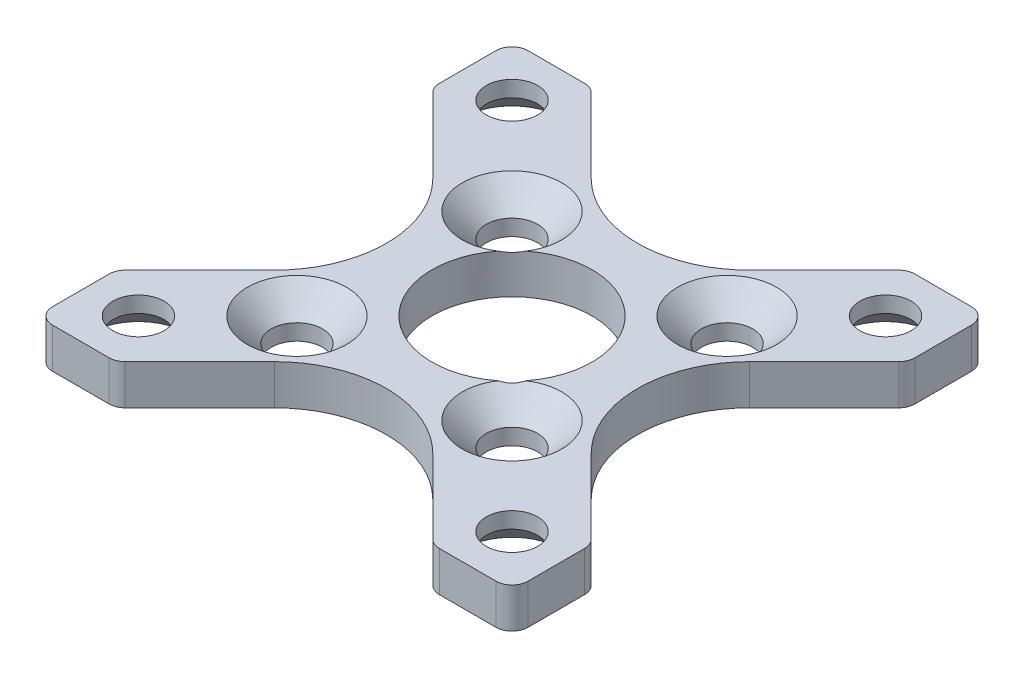
SolidWorks part; units mm, degrees
ref_plane "Front Plane" through (0, 0, 0) normal (0, 0, 1) x (1, 0, 0)
ref_plane "Top Plane" through (0, 0, 0) normal (0, 1, 0) x (1, 0, 0)
ref_plane "Right Plane" through (0, 0, 0) normal (1, 0, 0) x (0, 0, -1)
sketch "Sketch1" plane through (0, 0, 0) normal (0, 1, 0) x (1, 0, 0)
  line L0 (-6.7175, -14.8492) -> (-6.7175, 14.8492) construction
  line L1 (-14.8492, -14.8492) -> (14.8492, -14.8492)
  line L2 (-14.8492, -14.8492) -> (-14.8492, 14.8492)
  line L3 (-14.8492, 14.8492) -> (14.8492, 14.8492)
  line L4 (14.8492, -14.8492) -> (14.8492, 14.8492)
  line L5 (-14.8492, -14.8492) -> (14.8492, 14.8492) construction
  line L6 (-14.8492, 14.8492) -> (14.8492, -14.8492) construction
  line L7 (-14.8492, -6.7175) -> (14.8492, -6.7175) construction
  line L8 (6.7175, 14.8492) -> (6.7175, -14.8492) construction
  line L9 (14.8492, 6.7175) -> (-14.8492, 6.7175) construction
  circle A0 centre (0, 0) radius 5
  circle A1 centre (-5.6569, 5.6569) radius 1.6
  circle A2 centre (5.6569, -5.6569) radius 1.6
  circle A3 centre (-6.7175, -6.7175) radius 1.6
  circle A4 centre (6.7175, 6.7175) radius 1.6
  circle A5 centre (-11.6673, -11.6673) radius 1.6
  circle A6 centre (-11.6673, 11.6673) radius 1.6
  circle A7 centre (11.6673, 11.6673) radius 1.6
  circle A8 centre (11.6673, -11.6673) radius 1.6
  point P0 (0, 0)
  dimension "D3" = 10
  dimension "D7" = 3.2
  dimension "D1" = 42
  dimension "D2" = 13
  dimension "D4" = 13
  dimension "D5" = 11.5
  dimension "D6" = 11.5
  dimension "D8" = 4.5
  dimension "D9" = 4.5
  dimension "D10" = 4.5
  dimension "D11" = 4.5
extrude "Boss-Extrude1" add sketch "Sketch1" along normal blind 2.5
sketch "Sketch2" plane through (0, 2.5, 0) normal (0, 1, 0) x (1, 0, 0)
  line L0 (0, 14.8492) -> (0, -14.8492) construction
  line L1 (14.8492, 14.8492) -> (-14.8492, 14.8492) construction
  line L2 (-14.8492, -14.8492) -> (14.8492, -14.8492) construction
  line L3 (-14.8492, 0) -> (14.8492, 0) construction
  line L5 (-14.8492, 14.8492) -> (-14.8492, -14.8492) construction
  line L6 (14.8492, -14.8492) -> (14.8492, 14.8492) construction
  line L7 (-6.7175, -6.7175) -> (-6.7175, 6.7175) construction
  line L8 (-6.7175, 6.7175) -> (6.7175, 6.7175) construction
  line L9 (6.7175, 6.7175) -> (6.7175, -6.7175) construction
  line L10 (6.7175, -6.7175) -> (-6.7175, -6.7175) construction
  line L11 (-14.8492, -14.8492) -> (14.8492, 14.8492) construction
  line L12 (-14.8492, 14.8492) -> (14.8492, -14.8492) construction
  line L13 (-9.8995, 4.9497) -> (-14.8492, 9.8995)
  line L14 (-9.8995, -4.9497) -> (-14.8492, -9.8995)
  line L15 (-6.7175, 1.7678) -> (-9.8995, 4.9497) construction
  line L16 (-6.7175, -1.7678) -> (-9.8995, -4.9497) construction
  line L17 (-14.8492, 9.8995) -> (-14.8492, -9.8995)
  line L26 (9.8995, 14.8492) -> (-9.8995, 14.8492)
  line L27 (-4.9497, 9.8995) -> (-9.8995, 14.8492)
  line L28 (4.9497, 9.8995) -> (9.8995, 14.8492)
  line L29 (14.8492, -9.8995) -> (14.8492, 9.8995)
  line L30 (9.8995, 4.9497) -> (14.8492, 9.8995)
  line L31 (9.8995, -4.9497) -> (14.8492, -9.8995)
  line L32 (-9.8995, -14.8492) -> (9.8995, -14.8492)
  line L33 (4.9497, -9.8995) -> (9.8995, -14.8492)
  line L34 (-4.9497, -9.8995) -> (-9.8995, -14.8492)
  arc A0 (-9.8995, -4.9497) -> (-9.8995, 4.9497) centre (-14.8492, 0) ccw
  arc A4 (-9.8995, 4.9497) -> (-9.8995, -4.9497) centre (-14.8492, 0) ccw construction
  arc A8 (-4.9497, 9.8995) -> (4.9497, 9.8995) centre (0, 14.8492) ccw
  arc A9 (9.8995, 4.9497) -> (9.8995, -4.9497) centre (14.8492, 0) ccw
  arc A10 (4.9497, -9.8995) -> (-4.9497, -9.8995) centre (0, -14.8492) ccw
  point P49 (0, 0)
  dimension "D2" = 7
  dimension "D1" = 4
extrude "Cut-Extrude1" cut sketch "Sketch2" against normal through all
fillet "Fillet3" radius 1 12 edges at (-9.8995, 1.25, -14.8492) (-14.8492, 1.25, -14.8492) (-14.8492, 1.25, -9.8995) (-14.8492, 1.25, 9.8995) (-14.8492, 1.25, 14.8492) (-9.8995, 1.25, 14.8492) (9.8995, 1.25, 14.8492) (14.8492, 1.25, 14.8492) (14.8492, 1.25, 9.8995) (14.8492, 1.25, -9.8995) (9.8995, 1.25, -14.8492) (14.8492, 1.25, -14.8492)
chamfer "Chamfer1" distance 1.5 angle 45 8 edges at (6.7175, 2.5, -5.1175) (-5.6569, 2.5, -4.0569) (5.6569, 2.5, 7.2569) (-6.7175, 2.5, 8.3175) (11.6673, 0, 13.2673) (-11.6673, 0, 13.2673) (-11.6673, 0, -10.0673) (11.6673, 0, -10.0673)
